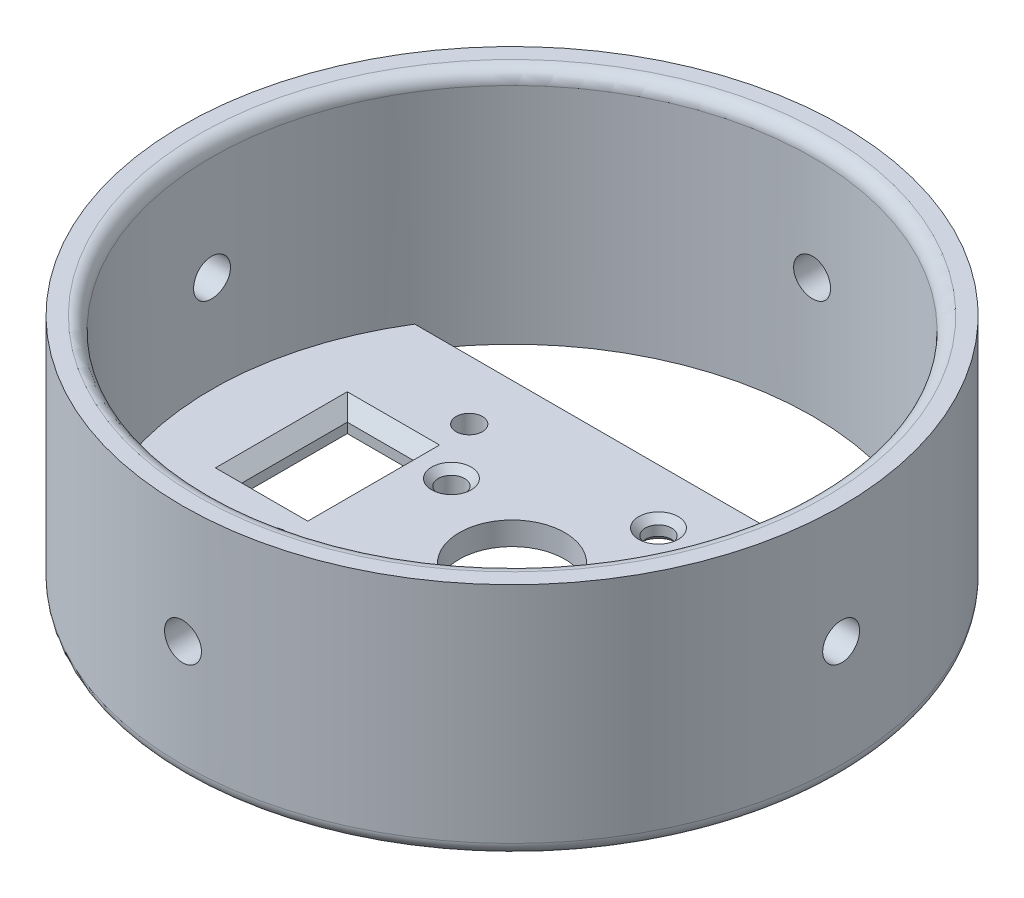
SolidWorks part; units mm, degrees
ref_plane "Front Plane" through (0, 0, 0) normal (0, 0, 1) x (1, 0, 0)
ref_plane "Top Plane" through (0, 0, 0) normal (0, 1, 0) x (1, 0, 0)
ref_plane "Right Plane" through (0, 0, 0) normal (1, 0, 0) x (0, 0, -1)
sketch "Sketch1" plane through (0, 0, 0) normal (0, 1, 0) x (1, 0, 0)
  line L0 (0, 8.5) -> (0, -8.5) construction
  line L1 (3.2528, 7.853) -> (-3.2528, -7.853) construction
  circle A0 centre (0, 0) radius 25
  circle A1 centre (0, 0) radius 4
  circle A2 centre (0, 0) radius 8.5 construction
  circle A3 centre (3.2528, 7.853) radius 1
  circle A4 centre (7.853, -3.2528) radius 1
  circle A5 centre (-3.2528, -7.853) radius 1
  circle A6 centre (-7.853, 3.2528) radius 1
  point P19 (0, 0)
  dimension "D1" = 50
  dimension "D2" = 8
  dimension "D3" = 17
  dimension "D5" = 2
  dimension "D4" = 22.5
  dimension "D6" = 4
extrude "Main Boss" add sketch "Sketch1" along normal blind 18
sketch "Sketch2" plane through (0, 18, 0) normal (0, 1, 0) x (1, 0, 0)
  circle A0 centre (0, 0) radius 22.8
  dimension "D1" = 45.6
extrude "Hollow" cut sketch "Sketch2" against normal offset from surface (16.25 mm away) 1.75 up to face at (0, 0, 25)
fillet "Fillet1" radius 1 2 edges at (0, 0, 25) (0, 18, 22.8)
sketch "Sketch3" plane through (0, 0, 0) normal (0, 0, 1) x (1, 0, 0)
  line L0 (25, 18) -> (-25, 18) construction
  circle A0 centre (0, 9.1) radius 1.4
  dimension "D2" = 2.8
  dimension "D1" = 8.9
extrude "External Screw Holes" cut sketch "Sketch3" against normal through all both and the other way through all
pattern_circular "CirPattern1" count 2 every 90 about axis through (0, -64.4881, 0) along (0, 1, 0) of "External Screw Holes"
sketch "Sketch4" plane through (0, 1.75, 0) normal (0, 1, 0) x (1, 0, 0)
  line L0 (-18.7307, 13) -> (18.7307, 13)
  line L1 (-18.7307, -13) -> (18.7307, -13)
  circle A0 centre (0, 0) radius 22.8 construction
  arc A1 (-18.7307, -13) -> (18.7307, -13) centre (0, 0) ccw
  arc A2 (18.7307, 13) -> (-18.7307, 13) centre (0, 0) ccw
  dimension "D1" = 26
extrude "Sensor Allowance" cut sketch "Sketch4" against normal through all
sketch "Sketch5" plane through (0, 1.75, 0) normal (0, 1, 0) x (1, 0, 0)
  line L0 (-16.5, 0) -> (16.5, 0) construction
  line L1 (-16.5, 4) -> (-11.5, 4)
  line L2 (-16.5, 4) -> (-16.5, -4)
  line L3 (-16.5, -4) -> (-11.5, -4)
  line L4 (-11.5, 4) -> (-11.5, -4)
  line L5 (11.5, 4) -> (16.5, 4)
  line L6 (11.5, 4) -> (11.5, -4)
  line L7 (11.5, -4) -> (16.5, -4)
  line L8 (16.5, 4) -> (16.5, -4)
  dimension "D1" = 5
  dimension "D2" = 8
  dimension "D3" = 23
extrude "Power Allowance" cut sketch "Sketch5" against normal through all
sketch "Sketch7" plane through (0, 0, 0) normal (0, -1, 0) x (1, 0, 0)
  line L0 (-12.5, -18.5) -> (1.75, -18.5)
  line L1 (-12.5, -18.5) -> (-12.5, -13)
  line L2 (1.75, -18.5) -> (1.75, -13)
  line L3 (-12.5, -13) -> (1.75, -13)
  line L4 (12.5, 13) -> (-1.75, 13)
  line L5 (12.5, -13) -> (12.5, -18.5)
  line L6 (12.5, -13) -> (2.25, -13)
  line L7 (12.5, -18.5) -> (2.25, -18.5)
  line L8 (2.25, -13) -> (2.25, -18.5)
  line L9 (-18.7307, -13) -> (18.7307, -13) construction
  line L10 (12.5, 18.5) -> (12.5, 13)
  line L11 (12.5, 18.5) -> (-1.75, 18.5)
  line L12 (-1.75, 18.5) -> (-1.75, 13)
  line L13 (-2.25, 13) -> (-2.25, 18.5)
  line L14 (-12.5, 13) -> (-2.25, 13)
  line L15 (-12.5, 18.5) -> (-2.25, 18.5)
  line L16 (-12.5, 13) -> (-12.5, 18.5)
  line L17 (18.7307, 13) -> (-18.7307, 13) construction
  line L18 (-12.5, -18.5) -> (-13.3263, -18.5) construction
  line L19 (12.5, -18.5) -> (13.3263, -18.5) construction
  line L20 (-12.5, 18.5) -> (-13.3263, 18.5) construction
  line L21 (12.5, 18.5) -> (13.3263, 18.5) construction
  arc A0 (-18.7307, -13) -> (18.7307, -13) centre (0, 0) ccw construction
  arc A1 (18.7307, 13) -> (-18.7307, 13) centre (0, 0) ccw construction
  point P23 (0, 0)
  dimension "D1" = 5.5
  dimension "D2" = 14.25
  dimension "D3" = 10.25
  dimension "D5" = 0.5
  dimension "D4" = 2
chamfer "Chamfer1" distance 1 angle 45 10 edges at (-14, 1.75, -4) (-16.5, 1.75, 0) (-14, 1.75, 4) (-11.5, 1.75, 0) (14, 1.75, -4) (16.5, 1.75, 0) (14, 1.75, 4) (11.5, 1.75, 0) (0, 1.75, -13) (0, 1.75, 13)
chamfer "Chamfer2" distance 0.5 angle 45 5 edges at (3.2528, 1.75, -6.853) (3.2528, 0, -6.853) (-3.2528, 1.75, 8.853) (7.853, 1.75, 4.2528) (-7.853, 1.75, -2.2528)
sketch "Sketch8" plane through (0, 1.75, 0) normal (0, 1, 0) x (1, 0, 0)
  line L0 (-10.75, 7.5) -> (10.75, 7.5) construction
  line L1 (10.75, 7.5) -> (10.75, -7.5) construction
  line L2 (10.75, -7.5) -> (-10.75, -7.5) construction
  line L3 (-10.75, -7.5) -> (-10.75, 7.5) construction
  line L4 (-10.75, 7.5) -> (10.75, -7.5) construction
  circle A0 centre (-10.75, 7.5) radius 1
  circle A1 centre (10.75, 7.5) radius 1
  circle A2 centre (-10.75, -7.5) radius 1
  circle A3 centre (10.75, -7.5) radius 1
  point P8 (0, 0)
  dimension "D3" = 2
  dimension "D1" = 15
  dimension "D2" = 21.5
extrude "Cut-Extrude1" cut sketch "Sketch8" against normal through all
